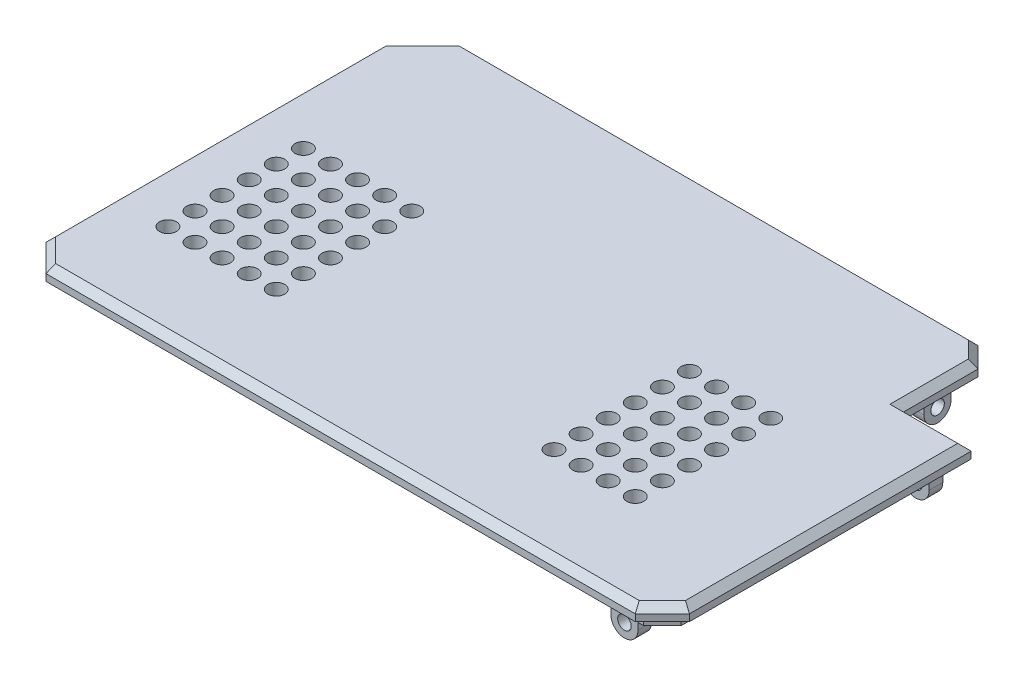
SolidWorks part; units mm, degrees
ref_plane "前视基准面" through (0, 0, 0) normal (0, 0, 1) x (1, 0, 0)
ref_plane "上视基准面" through (0, 0, 0) normal (0, 1, 0) x (1, 0, 0)
ref_plane "右视基准面" through (0, 0, 0) normal (1, 0, 0) x (0, 0, -1)
other "Configuration Table"
sketch "草图1" plane through (0, 0, 0) normal (0, 1, 0) x (1, 0, 0)
  line L3 (-10.9928, -16.6) -> (-6.9928, -12.6) construction
  line L4 (-10.9928, -16.6) -> (-97.9928, -16.6) construction
  line L5 (-101.9928, -12.6) -> (-97.9928, -16.6) construction
  line L10 (-16.9928, 40) -> (-16.9928, 29)
  line L11 (-16.9928, 29) -> (-6.9928, 29)
  line L12 (-6.9928, -12.6) -> (-6.9928, 29)
  line L13 (-10.9928, -16.6) -> (-6.9928, -12.6)
  line L14 (-10.9928, -16.6) -> (-97.9928, -16.6)
  line L15 (-101.9928, -12.6) -> (-97.9928, -16.6)
  line L16 (-101.9928, -12.6) -> (-101.9928, 37)
  line L17 (-95.9928, 43) -> (-101.9928, 37)
  line L18 (-19.9928, 43) -> (-95.9928, 43)
  line L19 (-16.9928, 40) -> (-19.9928, 43)
extrude "凸台-拉伸1" add sketch "草图1" along normal blind 2
sketch "草图2" plane through (0, 0, 0) normal (0, -1, 0) x (1, 0, 0)
  line L20 (-21.6911, -38.9) -> (-21.0928, -38.3017)
  line L21 (-21.0928, -38.3017) -> (-21.0928, -24.9)
  line L22 (-21.0928, -24.9) -> (-11.0928, -24.9)
  line L23 (-11.0928, -24.9) -> (-11.0928, 10.9017)
  line L24 (-11.0928, 10.9017) -> (-12.6911, 12.5)
  line L25 (-12.6911, 12.5) -> (-96.2945, 12.5)
  line L26 (-96.2945, 12.5) -> (-97.8928, 10.9017)
  line L27 (-97.8928, 10.9017) -> (-97.8928, -35.3017)
  line L28 (-97.8928, -35.3017) -> (-94.2945, -38.9)
  line L29 (-94.2945, -38.9) -> (-21.6911, -38.9)
  line L30 (-20.8626, -40.9) -> (-19.0928, -39.1302)
  line L31 (-19.0928, -39.1302) -> (-19.0928, -26.9)
  line L32 (-19.0928, -26.9) -> (-9.0928, -26.9)
  line L33 (-9.0928, -26.9) -> (-9.0928, 11.7302)
  line L34 (-9.0928, 11.7302) -> (-11.8626, 14.5)
  line L35 (-11.8626, 14.5) -> (-97.123, 14.5)
  line L36 (-97.123, 14.5) -> (-99.8928, 11.7302)
  line L37 (-99.8928, 11.7302) -> (-99.8928, -36.1302)
  line L38 (-99.8928, -36.1302) -> (-95.123, -40.9)
  line L39 (-95.123, -40.9) -> (-20.8626, -40.9)
  line L40 (-20.8626, -40.9) -> (-19.0928, -39.1302)
  line L41 (-19.0928, -39.1302) -> (-19.0928, -26.9)
  line L42 (-19.0928, -26.9) -> (-9.0928, -26.9)
  line L43 (-9.0928, -26.9) -> (-9.0928, 11.7302)
  line L44 (-9.0928, 11.7302) -> (-11.8626, 14.5)
  line L45 (-11.8626, 14.5) -> (-97.123, 14.5)
  line L46 (-97.123, 14.5) -> (-99.8928, 11.7302)
  line L47 (-99.8928, 11.7302) -> (-99.8928, -36.1302)
  line L48 (-99.8928, -36.1302) -> (-95.123, -40.9)
  line L49 (-95.123, -40.9) -> (-20.8626, -40.9)
  dimension "D1" = 2.1
  dimension "D2" = 2
extrude "凸台-拉伸2" add sketch "草图2" along normal blind 2
sketch "草图3" plane through (0, 2, 0) normal (0, 1, 0) x (1, 0, 0)
  line L0 (-6.9928, -12.6) -> (-6.9928, 29) construction
  line L1 (-97.9928, -16.6) -> (-10.9928, -16.6) construction
  line L2 (-101.9928, 37) -> (-101.9928, -12.6) construction
  circle A0 centre (-36.9928, -2.6) radius 1.25
  circle A1 centre (-32.9928, -2.6) radius 1.25
  circle A2 centre (-28.9928, -2.6) radius 1.25
  circle A3 centre (-24.9928, -2.6) radius 1.25
  circle A4 centre (-32.9928, 1.4) radius 1.25
  circle A5 centre (-28.9928, 1.4) radius 1.25
  circle A6 centre (-24.9928, 1.4) radius 1.25
  circle A7 centre (-32.9928, 5.4) radius 1.25
  circle A8 centre (-28.9928, 5.4) radius 1.25
  circle A9 centre (-24.9928, 5.4) radius 1.25
  circle A10 centre (-32.9928, 9.4) radius 1.25
  circle A11 centre (-28.9928, 9.4) radius 1.25
  circle A12 centre (-24.9928, 9.4) radius 1.25
  circle A13 centre (-36.9928, 1.4) radius 1.25
  circle A14 centre (-36.9928, 5.4) radius 1.25
  circle A15 centre (-36.9928, 9.4) radius 1.25
  circle A16 centre (-36.9928, 13.4) radius 1.25
  circle A17 centre (-32.9928, 13.4) radius 1.25
  circle A18 centre (-28.9928, 13.4) radius 1.25
  circle A19 centre (-24.9928, 13.4) radius 1.25
  circle A20 centre (-36.9928, 17.4) radius 1.25
  circle A21 centre (-32.9928, 17.4) radius 1.25
  circle A22 centre (-28.9928, 17.4) radius 1.25
  circle A23 centre (-24.9928, 17.4) radius 1.25
  circle A24 centre (-93.9928, -2.6) radius 1.25
  circle A25 centre (-89.9928, -2.6) radius 1.25
  circle A26 centre (-85.9928, -2.6) radius 1.25
  circle A27 centre (-81.9928, -2.6) radius 1.25
  circle A28 centre (-77.9928, -2.6) radius 1.25
  circle A29 centre (-89.9928, 1.4) radius 1.25
  circle A30 centre (-85.9928, 1.4) radius 1.25
  circle A31 centre (-81.9928, 1.4) radius 1.25
  circle A32 centre (-77.9928, 1.4) radius 1.25
  circle A33 centre (-89.9928, 5.4) radius 1.25
  circle A34 centre (-85.9928, 5.4) radius 1.25
  circle A35 centre (-81.9928, 5.4) radius 1.25
  circle A36 centre (-77.9928, 5.4) radius 1.25
  circle A37 centre (-89.9928, 9.4) radius 1.25
  circle A38 centre (-85.9928, 9.4) radius 1.25
  circle A39 centre (-81.9928, 9.4) radius 1.25
  circle A40 centre (-77.9928, 9.4) radius 1.25
  circle A41 centre (-89.9928, 13.4) radius 1.25
  circle A42 centre (-85.9928, 13.4) radius 1.25
  circle A43 centre (-81.9928, 13.4) radius 1.25
  circle A44 centre (-77.9928, 13.4) radius 1.25
  circle A45 centre (-89.9928, 17.4) radius 1.25
  circle A46 centre (-85.9928, 17.4) radius 1.25
  circle A47 centre (-81.9928, 17.4) radius 1.25
  circle A48 centre (-77.9928, 17.4) radius 1.25
  circle A49 centre (-93.9928, 1.4) radius 1.25
  circle A50 centre (-93.9928, 5.4) radius 1.25
  circle A51 centre (-93.9928, 9.4) radius 1.25
  circle A52 centre (-93.9928, 13.4) radius 1.25
  circle A53 centre (-93.9928, 17.4) radius 1.25
  dimension "D1" = 2.5
  dimension "D2" = 30
  dimension "D3" = 14
  dimension "D6" = 8
  dimension "D4" = 4
  dimension "D5" = 6
  dimension "D7" = 5
  dimension "D8" = 6
extrude "切除-拉伸1" cut sketch "草图3" against normal up to next (2 mm away)
sketch "草图4" plane through (0, -2, 0) normal (0, -1, 0) x (1, 0, 0)
  line L0 (-97.8928, 10.9017) -> (-97.8928, -35.3017) construction
  line L1 (-94.2945, -38.9) -> (-90.2945, -38.9)
  line L2 (-94.2945, -38.9) -> (-94.2945, -40.9)
  line L3 (-94.2945, -40.9) -> (-90.2945, -40.9)
  line L4 (-90.2945, -38.9) -> (-90.2945, -40.9)
  line L5 (-21.0928, -24.9) -> (-11.0928, -24.9) construction
  line L6 (-19.0928, -34.1272) -> (-21.0928, -34.1272)
  line L7 (-19.0928, -34.1272) -> (-19.0928, -38.1272)
  line L8 (-19.0928, -38.1272) -> (-21.0928, -38.1272)
  line L9 (-21.0928, -34.1272) -> (-21.0928, -38.1272)
  line L10 (-100.9928, 8.6) -> (-104.6576, 8.6) construction
  line L11 (-9.0928, -26.9) -> (-13.0928, -26.9)
  line L12 (-9.0928, -26.9) -> (-9.0928, -24.9)
  line L13 (-9.0928, -24.9) -> (-13.0928, -24.9)
  line L14 (-13.0928, -26.9) -> (-13.0928, -24.9)
  line L16 (-12.6911, 12.5) -> (-16.6911, 12.5)
  line L17 (-12.6911, 12.5) -> (-12.6911, 14.5)
  line L18 (-12.6911, 14.5) -> (-16.6911, 14.5)
  line L19 (-16.6911, 12.5) -> (-16.6911, 14.5)
  line L21 (-99.8928, 6.6) -> (-97.8928, 6.6)
  line L22 (-99.8928, 6.6) -> (-99.8928, 10.6)
  line L23 (-99.8928, 10.6) -> (-97.8928, 10.6)
  line L24 (-97.8928, 6.6) -> (-97.8928, 10.6)
  line L25 (-19.0928, -39.1302) -> (-19.0928, -26.9) construction
  line L26 (-95.123, -40.9) -> (-20.8626, -40.9) construction
  line L27 (-99.8928, 11.7302) -> (-99.8928, -36.1302) construction
  line L28 (-97.8928, -35) -> (-99.8928, -35)
  line L29 (-97.8928, -35) -> (-97.8928, -31)
  line L30 (-97.8928, -31) -> (-99.8928, -31)
  line L31 (-99.8928, -35) -> (-99.8928, -31)
  line L32 (-100.9928, -33) -> (-104.0952, -33) construction
  line L33 (-11.8626, 14.5) -> (-97.123, 14.5) construction
  line L34 (-17.9928, -36.1272) -> (-12.8761, -36.1272) construction
  point P6 (-99.8928, 8.6)
  point P36 (-97.8928, -33)
  point P41 (-21.0928, -36.1272)
  dimension "D1" = 4
  dimension "D2" = 4
  dimension "D3" = 4
  dimension "D4" = 4
  dimension "D5" = 4
extrude "凸台-拉伸3" add sketch "草图4" along normal blind 3
fillet "圆角1" radius 2 12 edges at (-16.6911, -5, 13.5) (-12.6911, -5, 13.5) (-9.0928, -5, -25.9) (-13.0928, -5, -25.9) (-20.0928, -5, -38.1272) (-20.0928, -5, -34.1272) (-94.2945, -5, -39.9) (-90.2945, -5, -39.9) (-98.8928, -5, 10.6) (-98.8928, -5, 6.6) (-98.8928, -5, -35) (-98.8928, -5, -31)
sketch "草图5" plane through (0, 0, -26.9) normal (0, 0, -1) x (-1, 0, 0)
  circle A0 centre (11.0928, -3) radius 1
  dimension "D1" = 2
extrude "切除-拉伸2" cut sketch "草图5" against normal up to next (2 mm away) draft 2
sketch "草图6" plane through (0, 0, 14.5) normal (0, 0, 1) x (1, 0, 0)
  circle A0 centre (-14.6911, -3) radius 1
  dimension "D1" = 2
extrude "切除-拉伸3" cut sketch "草图6" against normal up to next (2 mm away) draft 2
sketch "草图7" plane through (-99.8928, 0, 0) normal (-1, 0, 0) x (0, 0, 1)
  circle A0 centre (8.6, -2.85) radius 1
  circle A2 centre (-33, -2.85) radius 1
  dimension "D1" = 2
extrude "切除-拉伸4" cut sketch "草图7" against normal up to next (2 mm away) draft 2
sketch "草图8" plane through (0, 0, -40.9) normal (0, 0, -1) x (-1, 0, 0)
  circle A0 centre (92.2945, -3) radius 1
  dimension "D1" = 2
extrude "切除-拉伸5" cut sketch "草图8" against normal up to next (2 mm away) draft 2
sketch "草图9" plane through (-19.0928, 0, 0) normal (1, 0, 0) x (0, 0, -1)
  circle A1 centre (36.1302, -3) radius 1
  dimension "D1" = 2
extrude "切除-拉伸6" cut sketch "草图9" against normal up to next (2 mm away) draft 2
sketch "草图10" plane through (0, 0, 0) normal (0, -1, 0) x (1, 0, 0)
  line L0 (-19.9928, -43) -> (-95.9928, -43) construction
  line L1 (-71.9928, -29) -> (-69.9928, -29)
  line L2 (-71.9928, -29) -> (-71.9928, -21)
  line L3 (-71.9928, -21) -> (-69.9928, -21)
  line L4 (-69.9928, -29) -> (-69.9928, -21)
  line L5 (-49.9928, -29) -> (-47.9928, -29)
  line L6 (-49.9928, -29) -> (-49.9928, -21)
  line L7 (-49.9928, -21) -> (-47.9928, -21)
  line L8 (-47.9928, -29) -> (-47.9928, -21)
  line L9 (-101.9928, -37) -> (-101.9928, 12.6) construction
  dimension "D1" = 2
  dimension "D2" = 2
  dimension "D3" = 14
  dimension "D4" = 8
  dimension "D5" = 30
  dimension "D6" = 20
extrude "凸台-拉伸4" add sketch "草图10" along normal blind 2.85
sketch "草图11" plane through (0, -2.85, 0) normal (0, -1, 0) x (1, 0, 0)
  line L1 (-71.9928, -29) -> (-69.9928, -29)
  line L2 (-71.9928, -29) -> (-71.9928, -26.75)
  line L3 (-71.9928, -26.75) -> (-69.9928, -26.75)
  line L4 (-69.9928, -29) -> (-69.9928, -26.75)
  line L5 (-49.9928, -29) -> (-47.9928, -29)
  line L6 (-49.9928, -29) -> (-49.9928, -26.75)
  line L7 (-49.9928, -26.75) -> (-47.9928, -26.75)
  line L8 (-47.9928, -29) -> (-47.9928, -26.75)
  line L10 (-69.9928, -29) -> (-69.9928, -21) construction
  line L11 (-47.9928, -29) -> (-47.9928, -21) construction
  dimension "D1" = 2.25
extrude "凸台-拉伸5" add sketch "草图11" along normal blind 2
chamfer "倒角1" distance 1 angle 35 2 edges at (-48.9928, -4.85, -26.75) (-70.9928, -4.85, -26.75) first distance on face at (-48.9928, -3.85, -26.75) first distance on face at (-70.9928, -3.85, -26.75)
sketch "草图12" plane through (0, 0, 0) normal (0, -1, 0) x (1, 0, 0)
  line L1 (-20.9928, -2.1) -> (-18.9928, -2.1)
  line L2 (-20.9928, -2.1) -> (-20.9928, -6.9)
  line L3 (-20.9928, -6.9) -> (-18.9928, -6.9)
  line L4 (-18.9928, -2.1) -> (-18.9928, -6.9)
  line L5 (-97.9928, 16.6) -> (-10.9928, 16.6) construction
  line L6 (-6.9928, 12.6) -> (-6.9928, -29) construction
  dimension "D1" = 2
  dimension "D2" = 4.8
  dimension "D3" = 12
  dimension "D4" = 18.7
extrude "凸台-拉伸6" add sketch "草图12" along normal blind 7
chamfer "倒角2" distance 1 angle 35 1 edges at (-19.9928, -7, -6.9) first distance on face at (-19.9928, -3.5, -6.9)
sketch "草图13" plane through (0, 0, 0) normal (0, -1, 0) x (1, 0, 0)
  line L1 (-99.8928, -21.4) -> (-96.9928, -21.4)
  line L2 (-99.8928, -21.4) -> (-99.8928, -27.4)
  line L3 (-99.8928, -27.4) -> (-96.9928, -27.4)
  line L4 (-96.9928, -21.4) -> (-96.9928, -27.4)
  line L7 (-99.8928, 6.6) -> (-99.8928, -31) construction
  dimension "D1" = 2.9
extrude "凸台-拉伸7" add sketch "草图13" along normal blind 7
chamfer "倒角3" distance 1 angle 35 1 edges at (-96.9928, -7, -24.4) first distance on face at (-96.9928, -3.5, -24.4)
chamfer "倒角4" distance 1 angle 45 10 edges at (-99.9928, 2, 14.6) (-101.9928, 2, -12.2) (-98.9928, 2, -40) (-57.9928, 2, -43) (-18.4928, 2, -41.5) (-16.9928, 2, -34.5) (-11.9928, 2, -29) (-6.9928, 2, -8.2) (-54.4928, 2, 16.6) (-8.9928, 2, 14.6)
